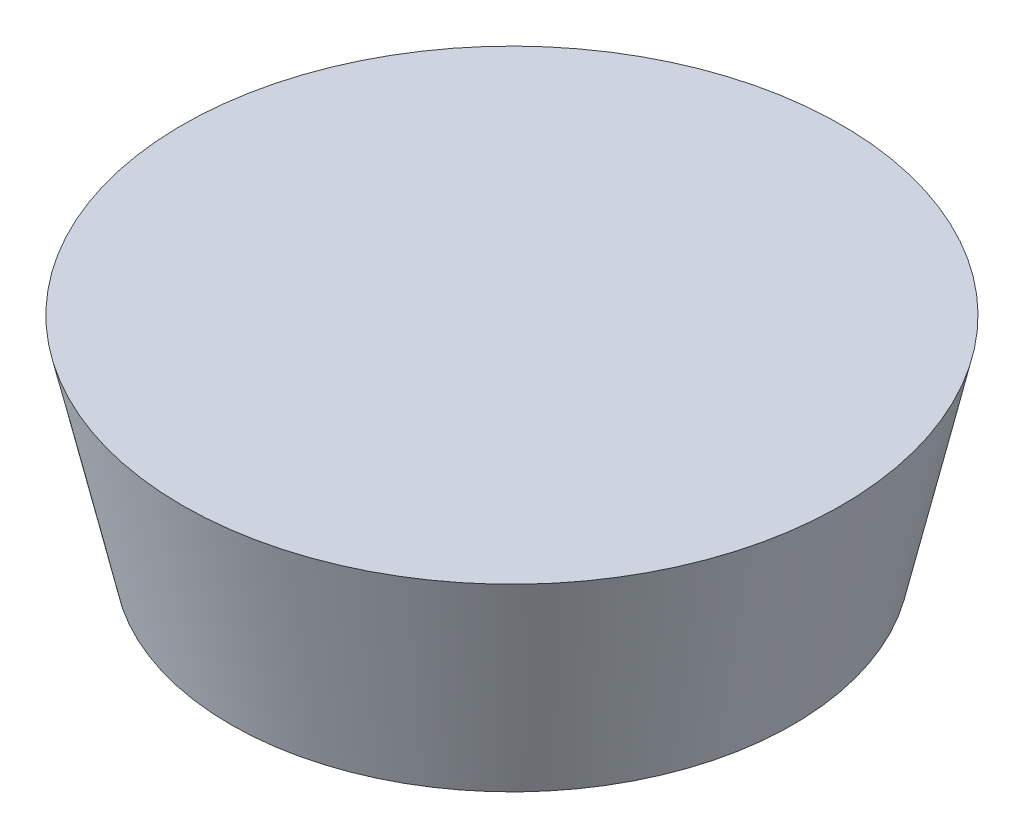
SolidWorks part; units mm, degrees
material "Silicon Rubber"
ref_plane "Front Plane" through (0, 0, 0) normal (0, 0, 1) x (1, 0, 0)
ref_plane "Top Plane" through (0, 0, 0) normal (0, 1, 0) x (1, 0, 0)
ref_plane "Right Plane" through (0, 0, 0) normal (1, 0, 0) x (0, 0, -1)
sketch "Sketch2" plane through (0, 0, 0) normal (0, 0, 1) x (1, 0, 0)
  line L0 (0, 0) -> (0, 25.4)
  line L1 (0, 25.4) -> (-22.4234, 25.4)
  line L2 (-22.4234, 25.4) -> (-16.6687, 0)
  line L3 (-16.6687, 0) -> (0, 0)
  dimension "D1" = 22.4234
  dimension "D2" = 16.6687
  dimension "D3" = 25.4
ref_axis "Axis1" through (0, 25.4, 0) along (0, -1, 0)
revolve "Revolve1" add sketch "Sketch2" angle 360 about L0
sketch "Sketch3" plane through (0, 25.4, 0) normal (0, 1, 0) x (1, 0, 0)
  circle A0 centre (0, 0) radius 25.4
  dimension "D1" = 50.8
extrude "Cut-Extrude1" cut sketch "Sketch3" against normal blind 12.7
